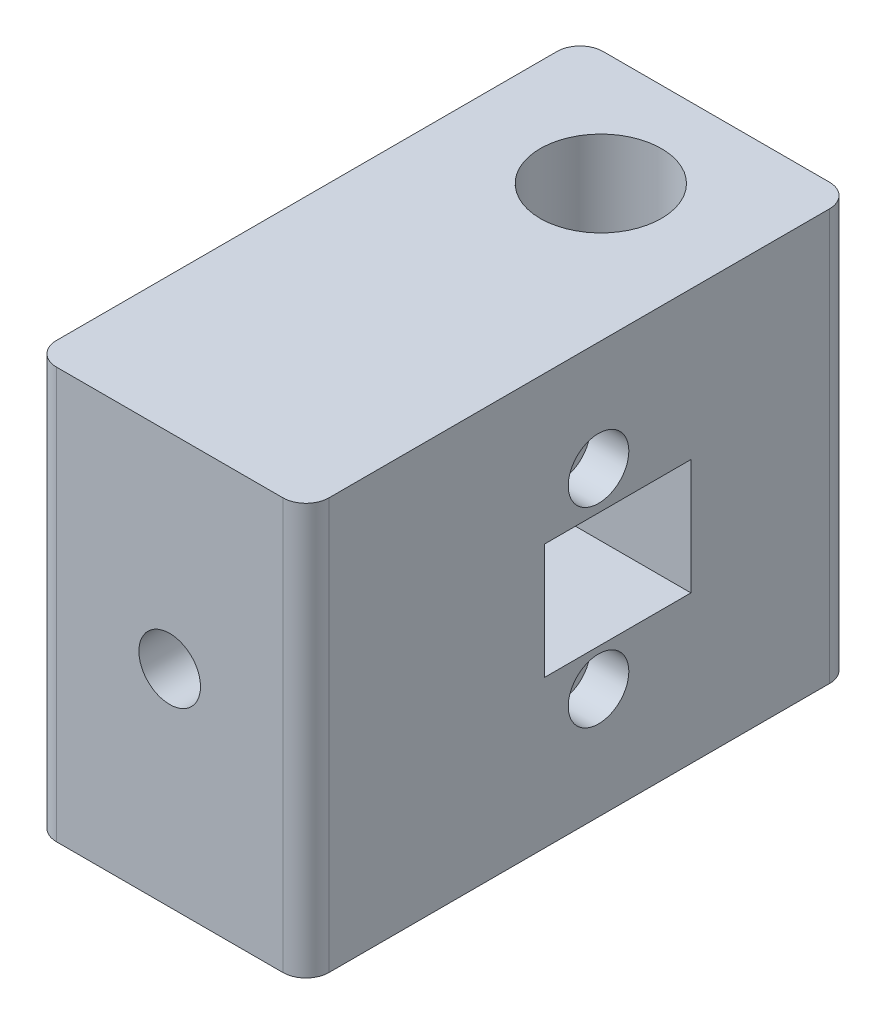
SolidWorks part; units mm, degrees
ref_plane "Front Plane" through (0, 0, 0) normal (0, 0, 1) x (1, 0, 0)
ref_plane "Top Plane" through (0, 0, 0) normal (0, 1, 0) x (1, 0, 0)
ref_plane "Right Plane" through (0, 0, 0) normal (1, 0, 0) x (0, 0, -1)
sketch "Sketch1" plane through (0, 0, 0) normal (0, 0, 1) x (1, 0, 0)
  line L1 (0, 0) -> (44.958, 0)
  line L2 (0, 0) -> (0, 67.818)
  line L3 (0, 67.818) -> (44.958, 67.818)
  line L4 (44.958, 0) -> (44.958, 67.818)
  dimension "D1" = 44.958
  dimension "D2" = 67.818
extrude "Boss-Extrude1" add sketch "Sketch1" along normal blind 90.17
sketch "Sketch2" plane through (44.958, 0, 0) normal (1, 0, 0) x (0, 0, -1)
  line L0 (-90.17, 0) -> (-90.17, 67.818) construction
  line L3 (-90.17, 0) -> (0, 0) construction
  circle A0 centre (-41.91, 49.788) radius 5
  circle A1 centre (-41.91, 18.288) radius 5
  point P4 (0, 0)
  point P5 (0, 0)
  dimension "D2" = 10
  dimension "D4" = 10
  dimension "D1" = 48.26
  dimension "D3" = 31.5
  dimension "D5" = 18.288
extrude "Cut-Extrude1" cut sketch "Sketch2" against normal blind 6.35
sketch "Sketch3" plane through (0, 67.818, 0) normal (0, 1, 0) x (1, 0, 0)
  line L0 (44.958, 0) -> (0, 0) construction
  line L1 (0, -90.17) -> (0, 0) construction
  circle A0 centre (22.479, -19.05) radius 4.064
  dimension "D1" = 8.128
  dimension "D2" = 19.05
  dimension "D3" = 22.479
extrude "Cut-Extrude2" cut sketch "Sketch3" against normal through all
sketch "Sketch4" plane through (0, 67.818, 0) normal (0, 1, 0) x (1, 0, 0)
  circle A0 centre (22.479, -19.05) radius 9.9949
  dimension "D1" = 19.9898
extrude "Cut-Extrude3" cut sketch "Sketch4" against normal blind 15.24
sketch "Sketch5" plane through (0, 0, 90.17) normal (0, 0, 1) x (1, 0, 0)
  line L0 (0, 0) -> (44.958, 0) construction
  line L1 (0, 67.818) -> (0, 0) construction
  circle A0 centre (22.479, 34.036) radius 5.08
  dimension "D3" = 10.16
  dimension "D1" = 34.036
  dimension "D2" = 22.479
extrude "Cut-Extrude4" cut sketch "Sketch5" against normal blind 50.8
sketch "Sketch6" plane through (44.958, 0, 0) normal (1, 0, 0) x (0, 0, -1)
  line L0 (-90.17, 0) -> (0, 0) construction
  line L1 (-50.8, 43.434) -> (-26.67, 43.434)
  line L2 (-50.8, 43.434) -> (-50.8, 24.384)
  line L3 (-50.8, 24.384) -> (-26.67, 24.384)
  line L4 (-26.67, 43.434) -> (-26.67, 24.384)
  line L5 (-90.17, 0) -> (-90.17, 67.818) construction
  dimension "D1" = 24.13
  dimension "D2" = 19.05
  dimension "D3" = 24.384
  dimension "D4" = 63.5
extrude "Cut-Extrude5" cut sketch "Sketch6" against normal blind 34.29
fillet "Fillet1" radius 3.81 4 edges at (0, 33.909, 0) (44.958, 33.909, 0) (0, 33.909, 90.17) (44.958, 33.909, 90.17)
